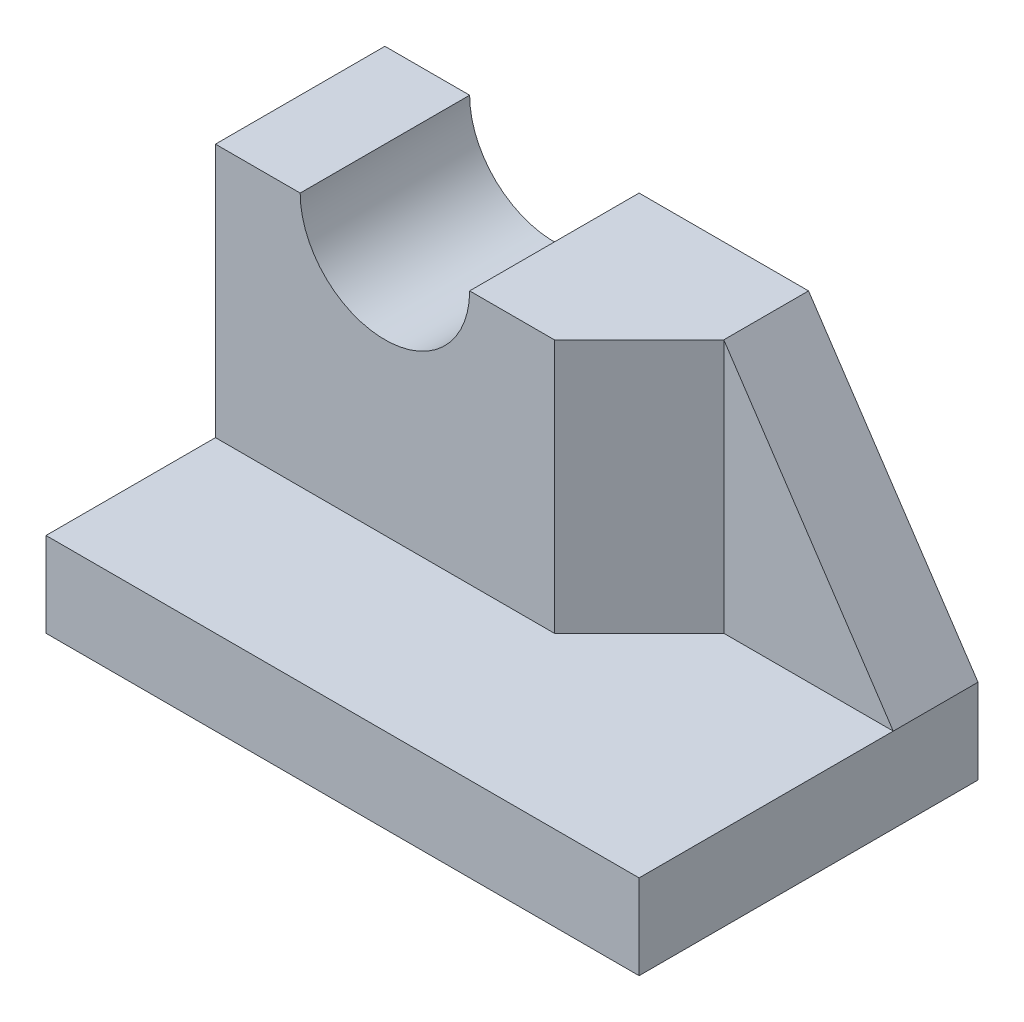
SolidWorks part; units mm, degrees
ref_plane "前基準面" through (0, 0, 0) normal (0, 0, 1) x (1, 0, 0)
ref_plane "上基準面" through (0, 0, 0) normal (0, 1, 0) x (1, 0, 0)
ref_plane "右基準面" through (0, 0, 0) normal (1, 0, 0) x (0, 0, -1)
sketch "草圖1" plane through (0, 0, 0) normal (0, 1, 0) x (1, 0, 0)
  line L0 (2.5, 0) -> (7.5, 5)
  line L1 (-17.5, -10) -> (17.5, -10)
  line L2 (-17.5, -10) -> (-17.5, 10)
  line L3 (-17.5, 10) -> (17.5, 10)
  line L4 (17.5, -10) -> (17.5, 10)
  line L5 (-17.5, -10) -> (17.5, 10) construction
  line L6 (-17.5, 10) -> (17.5, -10) construction
  line L7 (-17.5, 10) -> (-12.5, 10)
  line L8 (-17.5, 10) -> (-17.5, 0)
  line L9 (-17.5, 0) -> (-12.5, 0)
  line L10 (-12.5, 10) -> (-12.5, 0)
  line L11 (-12.5, 0) -> (2.5, 0)
  line L12 (-12.5, 0) -> (-12.5, 10)
  line L13 (-12.5, 10) -> (7.5, 10)
  line L14 (7.5, 5) -> (7.5, 10)
  line L15 (7.5, 10) -> (17.5, 10)
  line L16 (7.5, 10) -> (7.5, 5)
  line L17 (7.5, 5) -> (17.5, 5)
  line L18 (17.5, 10) -> (17.5, 5)
  point P0 (0, 0)
  point P10 (7.5, 0)
  dimension "D1" = 20
  dimension "D2" = 35
  dimension "D3" = 5
  dimension "D4" = 10
  dimension "D5" = 5
  dimension "D6" = 10
extrude "填料-伸長1" add sketch "草圖1" along normal blind 5 contours L10 L3 L2 L9 | L0 L14 L3 L10 L11 | L17 L0 L11 L9 L2 L1 L4 | L14 L17 L4 L3 region at (-3.0556, 0, -5.2222) region at (1.6919, 0, 3.8889) region at (12.5, 0, -7.5) region at (-15, 0, -5)
extrude "填料-伸長2" add sketch "草圖1<3>" along normal blind 20 contours L10 L3 L2 L9 | L0 L14 L3 L10 L11 | L14 L17 L4 L3 region at (-3.0556, 0, -5.2222) region at (12.5, 0, -7.5) region at (-15, 0, -5)
sketch "草圖1<3>" plane through (0, 0, 0) normal (0, 1, 0) x (1, 0, 0) same geometry as "草圖1"
sketch "草圖2" plane through (0, 0, 0) normal (0, 0, 1) x (1, 0, 0)
  line L0 (-7.5, 20) -> (-7.5, 11.813) construction
  line L1 (-17.5, 20) -> (2.5, 20) construction
  line L2 (-17.5, 20) -> (-17.5, 5) construction
  line L3 (-12.5, 20) -> (-2.5, 20)
  line L4 (17.5, 5) -> (7.5, 20)
  line L5 (7.5, 20) -> (17.5, 20) construction
  line L6 (7.5, 20) -> (17.5, 20)
  line L7 (17.5, 20) -> (17.5, 5) construction
  line L8 (17.5, 20) -> (17.5, 5)
  arc A0 (-12.5, 20) -> (-2.5, 20) centre (-7.5, 20) ccw
  dimension "D2" = 10
  dimension "D1" = 10
  dimension "D3" = 10
extrude "除料-伸長1" cut sketch "草圖2" against normal blind 20
